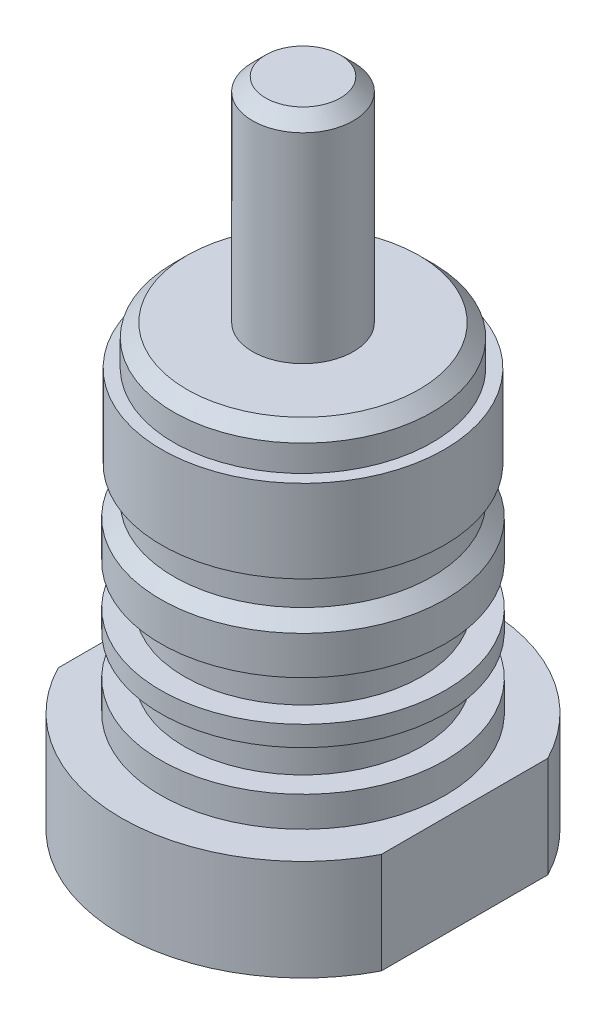
SolidWorks part; units mm, degrees
ref_plane "Plan de face" through (0, 0, 0) normal (0, 0, 1) x (1, 0, 0)
ref_plane "Plan de dessus" through (0, 0, 0) normal (0, 1, 0) x (1, 0, 0)
ref_plane "Plan de droite" through (0, 0, 0) normal (1, 0, 0) x (0, 0, -1)
sketch "Esquisse1" plane through (0, 0, 0) normal (0, 0, 1) x (1, 0, 0)
  line L0 (0, -21.75) -> (-9, -21.75)
  line L1 (-6.4, 0) -> (-2.5, 0)
  line L2 (-9, -21.75) -> (-9, -16.75)
  line L3 (-9, -16.75) -> (-7.05, -16.75)
  line L4 (-2.5, 0) -> (-2.5, 10.55)
  line L5 (-7.05, -16.75) -> (-7.05, -15.25)
  line L6 (-2.5, 10.55) -> (0, 10.55)
  line L7 (-7.05, -15.25) -> (-5.875, -15.25)
  line L8 (-5.875, -15.25) -> (-5.875, -13.25)
  line L9 (-5.875, -13.25) -> (-7.05, -13.25)
  line L10 (-7.05, -13.25) -> (-7.05, -12.25)
  line L11 (0, 10.55) -> (0, 0)
  line L12 (-7.05, -12.25) -> (-5.875, -12.25)
  line L13 (-5.875, -12.25) -> (-5.875, -10.25)
  line L14 (-7.05, -7.7) -> (-6.4, -7.7)
  line L15 (-5.875, -10.25) -> (-7.05, -10.25)
  line L16 (-7.05, -10.25) -> (-7.05, -7.7)
  line L18 (-6.4, -7.7) -> (-6.4, -6.05)
  line L19 (-6.4, -6.05) -> (-7, -6.05)
  line L20 (-7, -6.05) -> (-7, -1.95)
  line L21 (-7, -1.95) -> (-6.4, -1.95)
  line L22 (-6.4, -1.95) -> (-6.4, 0)
  line L23 (-6.4, 0) -> (0, 0) construction
  line L25 (0, 0) -> (0, -21.75)
  dimension "D1" = 7.05
  dimension "D2" = 1.5
  dimension "D3" = 1
  dimension "D4" = 5.875
  dimension "D5" = 5
  dimension "D6" = 9
  dimension "D7" = 21.75
  dimension "D8" = 6.4
  dimension "D9" = 7
  dimension "D10" = 1.95
  dimension "D11" = 4.1
  dimension "D12" = 1.65
  dimension "D13" = 2
  dimension "D14" = 2
  dimension "D15" = 2.5
  dimension "D16" = 10.55
revolve "Révolution1" add sketch "Esquisse1" angle 360 about L25
sketch "Esquisse2" plane through (0, -21.75, 0) normal (0, -1, 0) x (1, 0, 0)
  line L0 (8, 4.1231) -> (8, -4.1231)
  line L1 (-8, 4.1231) -> (-8, -4.1231)
  line L2 (0, 0) -> (0, 9) construction
  circle A0 centre (0, 0) radius 9 construction
  arc A1 (-8, 4.1231) -> (-8, -4.1231) centre (0, 0) ccw
  arc A2 (8, 4.1231) -> (8, -4.1231) centre (0, 0) cw
  dimension "D1" = 16
extrude "Enlèv. mat.-Extru.1" cut sketch "Esquisse2" against normal through all
chamfer "Chanfrein1" distance 0.65 angle 45 3 edges at (-6.4, 0, 0) (-2.5, 10.55, 0) (-7.05, -7.7, 0)
